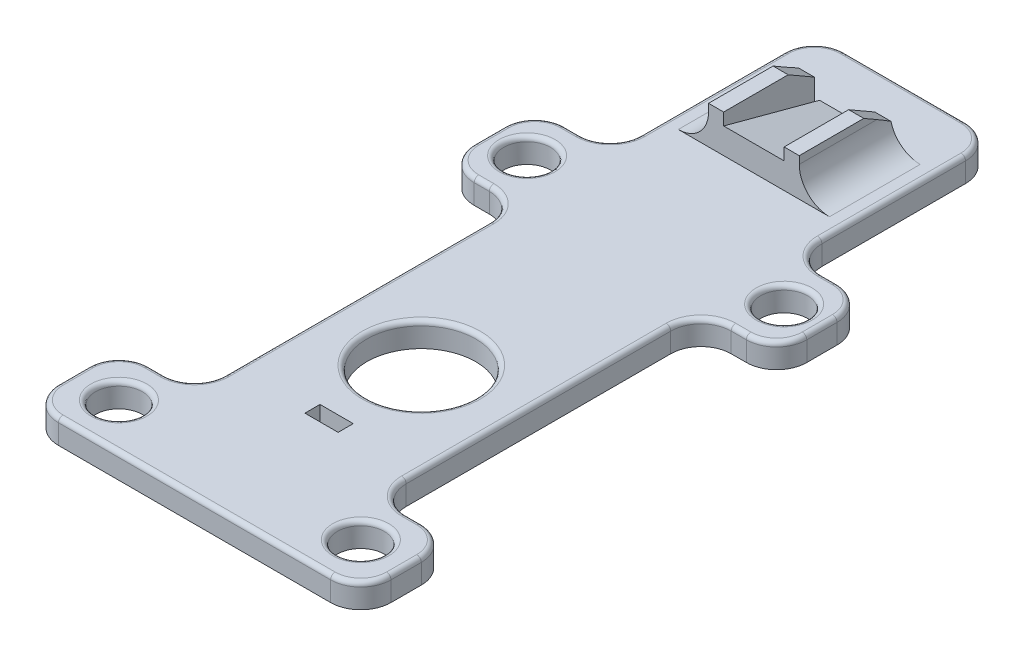
SolidWorks part; units mm, degrees
ref_plane "Front Plane" through (0, 0, 0) normal (0, 0, 1) x (1, 0, 0)
ref_plane "Top Plane" through (0, 0, 0) normal (0, 1, 0) x (1, 0, 0)
ref_plane "Right Plane" through (0, 0, 0) normal (1, 0, 0) x (0, 0, -1)
sketch "Sketch1" plane through (0, 0, 0) normal (0, 1, 0) x (1, 0, 0)
  line L1 (-6, -14) -> (6, -14)
  line L2 (-6, -14) -> (-6, 32)
  line L3 (-6, 32) -> (6, 32)
  line L4 (6, -14) -> (6, 32)
  line L5 (-6, -14) -> (6, 32) construction
  line L6 (-6, 32) -> (6, -14) construction
  point P0 (0, 9)
  dimension "D1" = 14
  dimension "D2" = 32
  dimension "D3" = 12
extrude "Boss-Extrude1" add sketch "Sketch1" along normal blind 1.6
sketch "Sketch2" plane through (0, 0, 0) normal (0, 1, 0) x (1, 0, 0)
  circle A0 centre (0, 0) radius 3.6
  dimension "D1" = 7.2
extrude "Cut-Extrude1" cut sketch "Sketch2" along normal through all
sketch "Sketch3" plane through (0, 0, 0) normal (0, -1, 0) x (1, 0, 0)
  line L0 (-6, 14) -> (6, 14) construction
  line L1 (2.5, 14) -> (-2.5, 14)
  line L2 (2.5, 14) -> (2.5, 13)
  line L3 (2.5, 13) -> (-2.5, 13)
  line L4 (-2.5, 14) -> (-2.5, 13)
  point P6 (0, 13)
  dimension "D1" = 1
  dimension "D2" = 5
extrude "Boss-Extrude2" [suppressed] add sketch "Sketch3" along normal blind 2.1
sketch "Sketch4" [suppressed] plane through (0, -2.1, 0) normal (0, -1, 0) x (1, 0, 0)
  line L0 (2.5, 14.2) -> (2.5, 15.2) construction
  line L1 (-2.5, 15.2) -> (2.5, 15.2)
  line L2 (-2.5, 15.2) -> (-2.5, 12.2)
  line L3 (-2.5, 12.2) -> (2.5, 12.2)
  line L4 (2.5, 15.2) -> (2.5, 12.2)
  dimension "D1" = 3
extrude "Boss-Extrude3" [suppressed] add sketch "Sketch4" along normal blind 1
sketch "Sketch5" plane through (0, 1.6, 0) normal (0, 1, 0) x (1, 0, 0)
  line L1 (-11, 12.5) -> (11, 12.5)
  line L2 (-11, 12.5) -> (-11, 18.5)
  line L3 (-11, 18.5) -> (11, 18.5)
  line L4 (11, 12.5) -> (11, 18.5)
  line L5 (-11, 12.5) -> (11, 18.5) construction
  line L6 (-11, 18.5) -> (11, 12.5) construction
  line L7 (-11, -15) -> (11, -15)
  line L8 (-11, -15) -> (-11, -9)
  line L9 (-11, -9) -> (11, -9)
  line L10 (11, -15) -> (11, -9)
  line L11 (-11, -15) -> (11, -9) construction
  line L12 (-11, -9) -> (11, -15) construction
  point P0 (0, 15.5)
  point P5 (0, -12)
  dimension "D1" = 6
  dimension "D2" = 22
  dimension "D3" = 15.5
  dimension "D4" = 12
  dimension "D5" = 6
  dimension "D6" = 22
extrude "Boss-Extrude4" add sketch "Sketch5" against normal up to vertex (1.6 mm away) up to point (-6, 0, -32)
sketch "Sketch6" plane through (0, 1.6, 0) normal (0, 1, 0) x (1, 0, 0)
  line L0 (11, 12.5) -> (11, 18.5) construction
  circle A0 centre (-8.5, 15.5) radius 1.55
  circle A1 centre (8.5, 15.5) radius 1.55
  circle A2 centre (8, -12) radius 1.55
  circle A3 centre (-8, -12) radius 1.55
  point P8 (11, 15.5)
  dimension "D2" = 3.1
  dimension "D1" = 8.5
  dimension "D3" = 8.5
  dimension "D4" = 12
  dimension "D5" = 8
  dimension "D6" = 8
extrude "Cut-Extrude2" cut sketch "Sketch6" against normal through all
fillet "Fillet1" radius 2 16 edges at (6, 0.8, -32) (-6, 0.8, -32) (6, 0.8, -12.5) (11, 0.8, -12.5) (6, 0.8, -18.5) (11, 0.8, -18.5) (-6, 0.8, -18.5) (-11, 0.8, -18.5) (-6, 0.8, -12.5) (-11, 0.8, -12.5) (11, 0.8, 15) (11, 0.8, 9) (-11, 0.8, 15) (-11, 0.8, 9) (6, 0.8, 9) (-6, 0.8, 9)
fillet "Fillet2" radius 0.3 37 edges at (0, 1.6, 3.6) (-6.5858, 1.6, -11.9142) (-10.4142, 1.6, -13.0858) (-11, 1.6, -15.5) (-10.4142, 1.6, -17.9142) (-6.5858, 1.6, -19.0858) (-6, 1.6, -25.25) (-5.4142, 1.6, -31.4142) (0, 1.6, -32) (5.4142, 1.6, -31.4142) (6, 1.6, -25.25) (6.5858, 1.6, -19.0858) (10.4142, 1.6, -17.9142) (11, 1.6, -15.5) (10.4142, 1.6, -13.0858) (6.5858, 1.6, -11.9142) (6, 1.6, -1.75) (-6, 1.6, -1.75) (8.5, 1.6, -13.95) (-8.5, 1.6, -13.95) (-8.5, 1.6, -12.5) (-8.5, 1.6, -18.5) (8.5, 1.6, -18.5) (8.5, 1.6, -12.5) (-11, 1.6, 12) (11, 1.6, 12) (0, 1.6, 15) (-8, 1.6, 13.55) (8, 1.6, 13.55) (-10.4142, 1.6, 14.4142) (-10.4142, 1.6, 9.5858) (-8.5, 1.6, 9) (-6.5858, 1.6, 8.4142) (6.5858, 1.6, 8.4142) (8.5, 1.6, 9) (10.4142, 1.6, 9.5858) (10.4142, 1.6, 14.4142)
sketch "Sketch7" plane through (0, 1.6, 0) normal (0, 1, 0) x (1, 0, 0)
  line L0 (-4, 18.8) -> (-4, 17.2)
  line L1 (-4, 28.8) -> (4, 28.8)
  line L2 (-4, 28.8) -> (-4, 27.2)
  line L3 (-4, 27.2) -> (4, 27.2)
  line L4 (4, 28.8) -> (4, 27.2)
  line L5 (-4, 18.8) -> (4, 18.8)
  line L6 (4, 18.8) -> (4, 17.2)
  line L7 (-4, 17.2) -> (4, 17.2)
  line L8 (-4, 8.8) -> (-4, 7.2)
  line L9 (-4, 8.8) -> (4, 8.8)
  line L10 (4, 8.8) -> (4, 7.2)
  line L11 (-4, 7.2) -> (4, 7.2)
  point P4 (0, 27.2)
  point P6 (4, 28)
  point P7 (4, 18)
  dimension "D1" = 1.6
  dimension "D2" = 8
  dimension "D3" = 28
  dimension "D5" = 10
  dimension "D4" = 3
extrude "Boss-Extrude5" [suppressed] add sketch "Sketch7" along normal blind 2.4
fillet "Fillet4" [suppressed] radius 2.4
sketch "Sketch8" plane through (0, 1.6, 0) normal (0, 1, 0) x (1, 0, 0)
  line L1 (-3, 22) -> (3, 22)
  line L2 (-3, 22) -> (-3, 28)
  line L3 (-3, 28) -> (3, 28)
  line L4 (3, 22) -> (3, 28)
  line L5 (-3, 22) -> (3, 28) construction
  line L6 (-3, 28) -> (3, 22) construction
  line L7 (2, 22) -> (-2, 22)
  line L8 (2, 22) -> (2, 28)
  line L9 (2, 28) -> (-2, 28)
  line L10 (-2, 22) -> (-2, 28)
  line L11 (2, 22) -> (-2, 28) construction
  line L12 (2, 28) -> (-2, 22) construction
  point P0 (0, 25)
  point P5 (0, 25)
  dimension "D1" = 22
  dimension "D2" = 6
  dimension "D3" = 6
  dimension "D4" = 4
extrude "Boss-Extrude6" add sketch "Sketch8" along normal blind 2.5 contours L1 L10 L3 L2 | L8 L1 L4 L3 region at (-2.5, 1.6, -25) region at (2.5, 1.6, -25)
sketch "Sketch9" plane through (-2, 0, 0) normal (1, 0, 0) x (0, 0, -1)
  line L0 (22, 1.6) -> (28.3445, 1.6)
  line L1 (28.3445, 1.6) -> (22, 3.3)
  line L2 (22, 4.1) -> (22, 1.6) construction
  line L3 (22, 3.3) -> (22, 1.6)
  dimension "D1" = 15
  dimension "D2" = 1.7
extrude "Boss-Extrude7" add sketch "Sketch9" along normal up to vertex (4 mm away) up to point (2, 4.1, -22)
sketch "Sketch10" plane through (0, 0, 0) normal (0, -1, 0) x (1, 0, 0)
  line L1 (1.1, 6.6) -> (-1.1, 6.6)
  line L2 (1.1, 6.6) -> (1.1, 5.6)
  line L3 (1.1, 5.6) -> (-1.1, 5.6)
  line L4 (-1.1, 6.6) -> (-1.1, 5.6)
  line L5 (1.1, 6.6) -> (-1.1, 5.6) construction
  line L6 (1.1, 5.6) -> (-1.1, 6.6) construction
  point P0 (0, 6.1)
  point P5 (0, 0)
  dimension "D1" = 6.6
  dimension "D2" = 1
  dimension "D3" = 2.2
extrude "Cut-Extrude3" cut sketch "Sketch10" against normal through all
chamfer "Chamfer1" distance 1 angle 60 2 edges at (-2.5, 4.1, -28) (2.5, 4.1, -28) first distance on face at (-2.4, 2.6185, -28) first distance on face at (2.4, 2.6185, -28)
fillet "Fillet5" radius 2 2 edges at (3, 1.6, -25) (-3, 1.6, -25)
equation "\"D3@Sketch6\"=\"D1@Sketch6\""
equation "\"D6@Sketch6\"=\"D5@Sketch6\""
